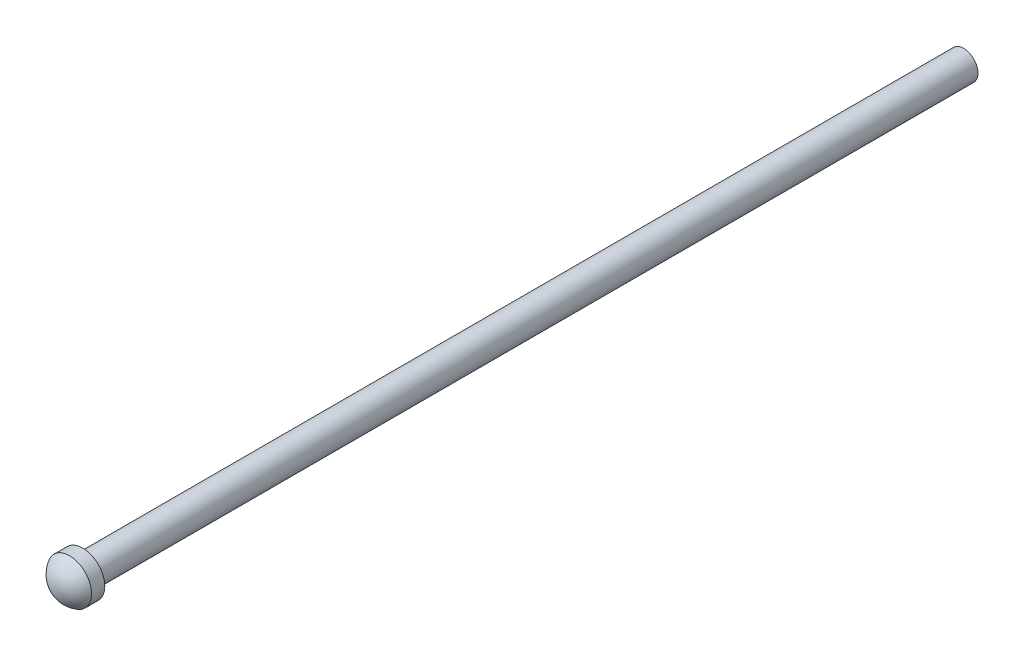
SolidWorks part; units mm, degrees
ref_plane "Front Plane" through (0, 0, 0) normal (0, 0, 1) x (1, 0, 0)
ref_plane "Top Plane" through (0, 0, 0) normal (0, 1, 0) x (1, 0, 0)
ref_plane "Right Plane" through (0, 0, 0) normal (1, 0, 0) x (0, 0, -1)
sketch "Sketch2" plane through (0, 0, 0) normal (0, 0, 1) x (1, 0, 0)
  circle A2 centre (5, 60) radius 3.25
  circle A3 centre (5, 60) radius 3.25
  dimension "D1" = 0.25
sketch "Sketch7" plane through (0, 0, 0) normal (1, 0, 0) x (0, 0, -1)
  line L0 (0, 0) -> (200, 0) construction
  line L1 (0, 0) -> (200, 0)
sweep "Sweep1" add profiles "Sketch2" path "Sketch7"
sketch "Sketch8" plane through (0, 0, 0) normal (0, 0, 1) x (1, 0, 0)
  circle A0 centre (5, 60) radius 5
  arc A1 (5, 55) -> (0, 60) centre (5, 60) ccw construction
extrude "Boss-Extrude1" add sketch "Sketch8" along normal blind 3
dome "Dome1" faces to dome 1 distance 3 reverse direction no elliptical dome no face at (10, 60, 3) parameters "D1"=3
